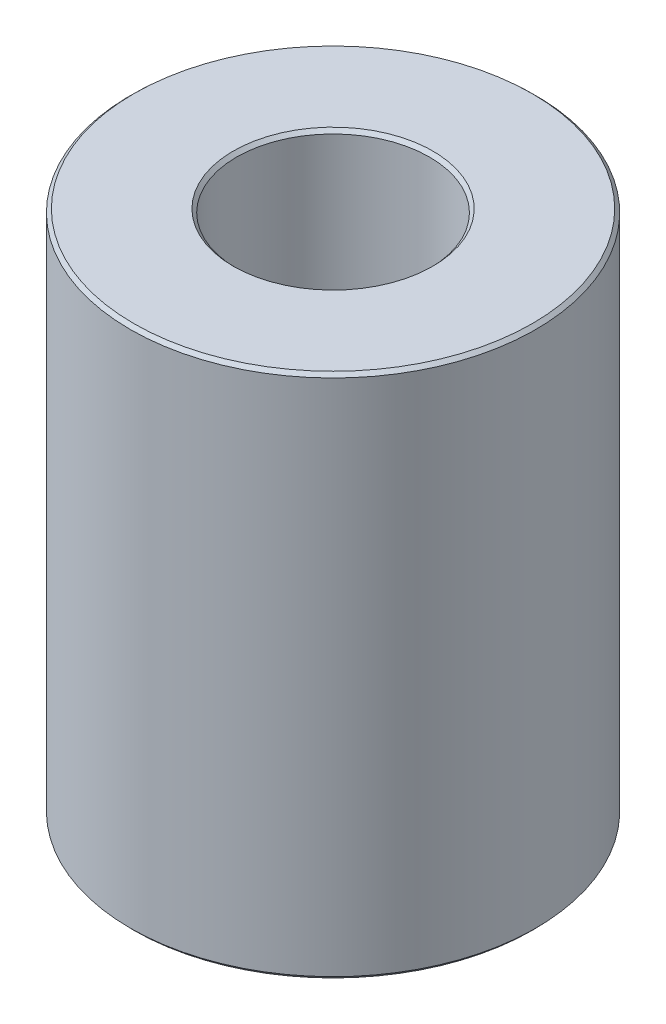
SolidWorks part; units mm, degrees
ref_plane "Front Plane" through (0, 0, 0) normal (0, 0, 1) x (1, 0, 0)
ref_plane "Top Plane" through (0, 0, 0) normal (0, 1, 0) x (1, 0, 0)
ref_plane "Right Plane" through (0, 0, 0) normal (1, 0, 0) x (0, 0, -1)
sketch "Sketch1" plane through (0, 0, 0) normal (0, 1, 0) x (1, 0, 0)
  circle A0 centre (0, 0) radius 60
  dimension "SLEEVE_OD" = 120
extrude "Boss-Extrude1" add sketch "Sketch1" along normal blind 155.5023
sketch "Sketch2" plane through (0, 0, 0) normal (0, 1, 0) x (1, 0, 0)
  circle A0 centre (0, 0) radius 28.5499
  dimension "BORE_D" = 57.0998
extrude "Cut-Extrude1" cut sketch "Sketch2" along normal through all
chamfer "Chamfer1" distance 0.9948 angle 46.291 4 edges at (0, 155.5023, 28.5499) (0, 0, 28.5499) (0, 0, 60) (0, 155.5023, 60) first distance on face at (0, 155.5023, 28.5499) first distance on face at (0, 0, 28.5499) first distance on face at (0, 155.5023, 60)
